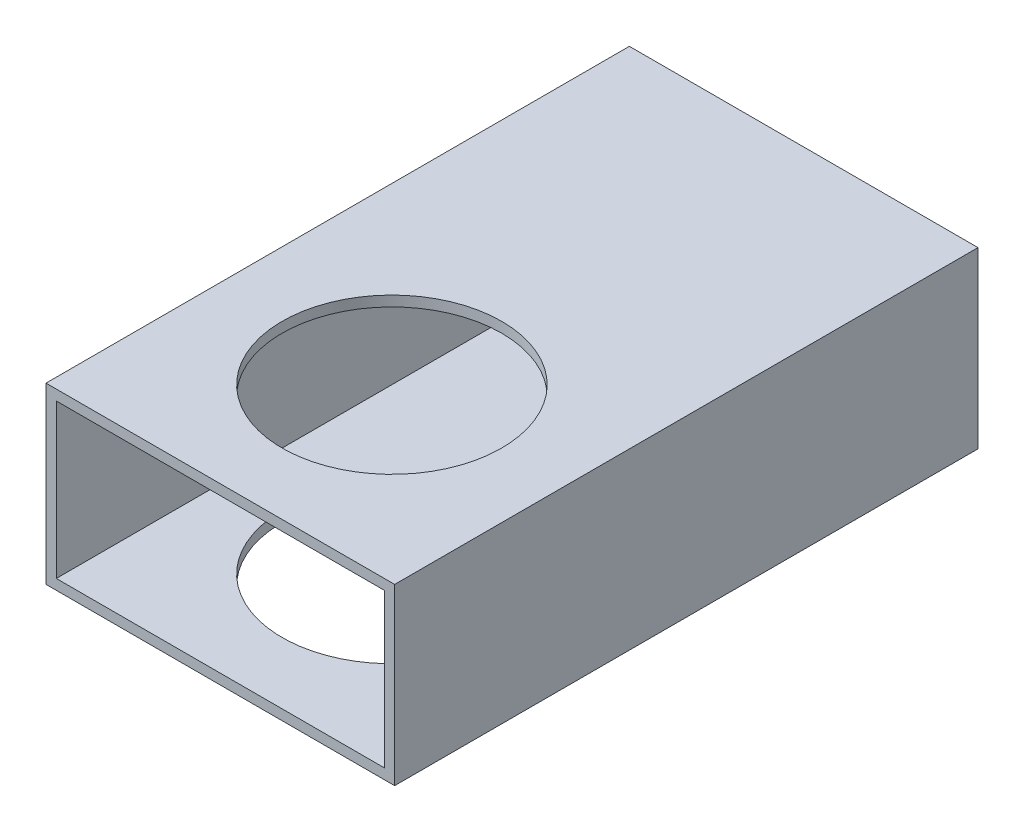
SolidWorks part; units mm, degrees
material "AISI 1015 Acero estirado en frío (SS)"
ref_plane "Alzado" through (0, 0, 0) normal (0, 0, 1) x (1, 0, 0)
ref_plane "Planta" through (0, 0, 0) normal (0, 1, 0) x (1, 0, 0)
ref_plane "Vista lateral" through (0, 0, 0) normal (1, 0, 0) x (0, 0, -1)
sketch "Croquis1" plane through (0, 0, 0) normal (0, 0, 1) x (1, 0, 0)
  line L0 (-23.9, -11.2) -> (-23.9, 11.2)
  line L1 (-25.4, -12.7) -> (25.4, -12.7)
  line L2 (-25.4, -12.7) -> (-25.4, 12.7)
  line L3 (-25.4, 12.7) -> (25.4, 12.7)
  line L4 (25.4, -12.7) -> (25.4, 12.7)
  line L5 (-25.4, -12.7) -> (25.4, 12.7) construction
  line L6 (-25.4, 12.7) -> (25.4, -12.7) construction
  line L7 (-23.9, 11.2) -> (23.9, 11.2)
  line L8 (23.9, -11.2) -> (23.9, 11.2)
  line L9 (-23.9, -11.2) -> (23.9, -11.2)
  point P0 (0, 0)
  dimension "D1" = 25.4
  dimension "D2" = 50.8
  dimension "D3" = 1.5
extrude "Saliente-Extruir1" add sketch "Croquis1" along normal blind 85
ref_plane "Plano1" through (0, -12.7, 0) normal (0, -1, 0) x (-1, 0, 0)
sketch "Croquis2" plane through (0, -12.7, 0) normal (0, -1, 0) x (-1, 0, 0)
  line L0 (0, -85) -> (0, 0) construction
  line L1 (25.4, -85) -> (-25.4, -85) construction
  line L2 (25.4, 0) -> (-25.4, 0) construction
  circle A0 centre (0, -60) radius 16
  dimension "D2" = 32
  dimension "D1" = 60
extrude "Cortar-Extruir1" cut sketch "Croquis2" against normal blind 26
